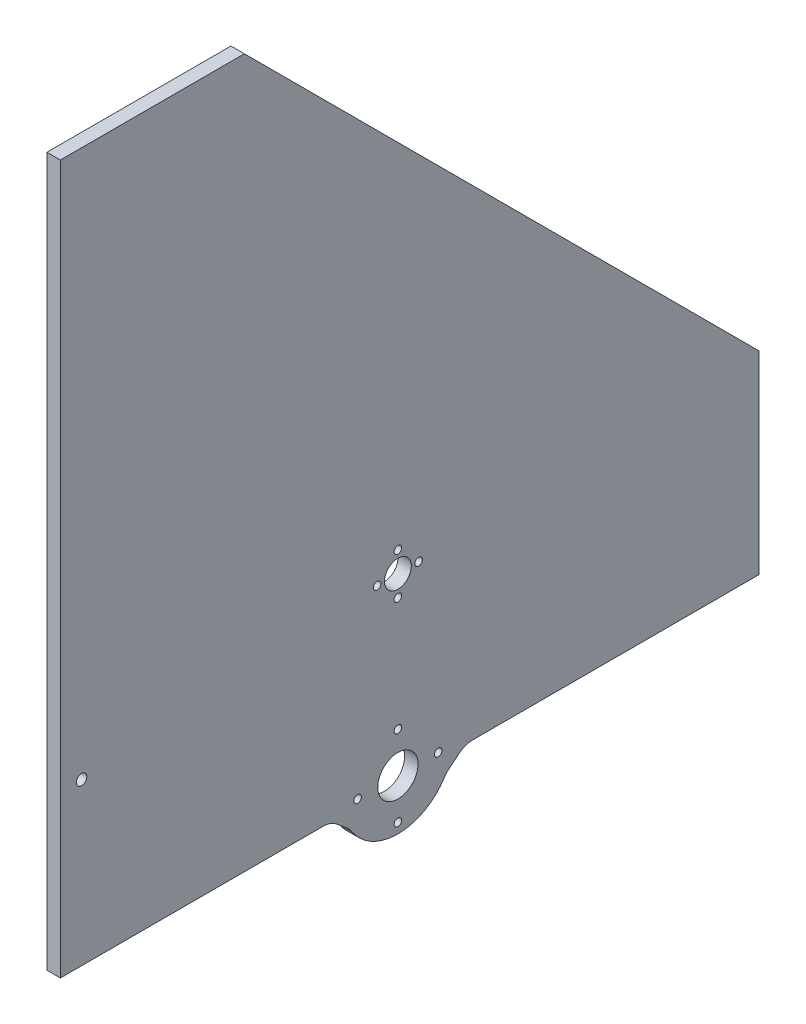
SolidWorks part; units mm, degrees
ref_plane "Front Plane" through (0, 0, 0) normal (0, 0, 1) x (1, 0, 0)
ref_plane "Top Plane" through (0, 0, 0) normal (0, 1, 0) x (1, 0, 0)
ref_plane "Right Plane" through (0, 0, 0) normal (1, 0, 0) x (0, 0, -1)
sketch "Sketch1" plane through (0, 0, 0) normal (1, 0, 0) x (0, 0, -1)
  line L0 (330.2, 112.3614) -> (86.9614, 355.6)
  line L1 (0, 0) -> (330.2, 0)
  line L2 (0, 0) -> (0, 355.6)
  line L3 (0, 355.6) -> (86.9614, 355.6)
  line L4 (330.2, 0) -> (330.2, 112.3614)
  point P1 (171.4728, 228.6)
  point P7 (105.7678, 228.6)
  point P8 (182.6629, 228.6)
  point P9 (110.0595, 228.6)
  point P10 (330.2, 66.1679)
  point P11 (148.4572, 228.6)
  point P12 (161.5636, 228.6)
  point P13 (172.5781, 228.6)
  point P14 (113.9067, 323.85)
  point P15 (113.028, 323.85)
  point P16 (86.9614, 355.6)
  dimension "D3" = 135
  dimension "D1" = 330.2
  dimension "D2" = 355.6
extrude "Main Plate Size" add sketch "Sketch1" along normal blind 6.35
sketch "Sketch2" plane through (6.35, 0, 0) normal (1, 0, 0) x (0, 0, -1)
  line L0 (178.562, 23.8252) -> (159.512, 42.8752) construction
  line L1 (0, 0) -> (330.2, 0) construction
  line L2 (178.562, 23.8252) -> (159.512, 4.7752) construction
  line L3 (159.512, 42.8752) -> (140.462, 23.8252) construction
  line L4 (159.512, 4.7752) -> (140.462, 23.8252) construction
  line L5 (178.562, 23.8252) -> (140.462, 23.8252) construction
  line L6 (159.512, 42.8752) -> (159.512, 4.7752) construction
  line L7 (0, 355.6) -> (0, 0) construction
  line L9 (0, 20.8026) -> (134.112, 20.8026)
  line L10 (184.912, 20.8026) -> (330.2, 20.8026)
  line L11 (330.2, 0) -> (330.2, 112.3614) construction
  line L12 (0, 20.8026) -> (0, 0)
  line L13 (330.2, 0) -> (330.2, 20.8026)
  line L15 (0, 0) -> (177.8, 0)
  line L16 (177.8, 0) -> (330.2, 0)
  circle A0 centre (159.512, 23.8252) radius 9.525
  circle A1 centre (159.512, 42.8752) radius 1.778
  circle A2 centre (178.562, 23.8252) radius 1.778
  circle A3 centre (159.512, 4.7752) radius 1.778
  circle A4 centre (140.462, 23.8252) radius 1.778
  arc A5 (134.112, 20.8026) -> (184.912, 20.8026) centre (159.512, 25.908) ccw
  point P24 (134.112, 20.8026)
  line M11 (0, 355.6) -> (0, 0)
  line M12 (0, 0) -> (330.2, 0)
  line M13 (330.2, 0) -> (330.2, 112.3614)
  dimension "D1" = 19.05
  dimension "D2" = 3.556
  dimension "D6" = 25.908
  dimension "D3" = 38.1
  dimension "D4" = 159.512
  dimension "D5" = 5.1054
  dimension "D7" = 2.0828
extrude "Bottom Shaft Mounting Holes" cut sketch "Sketch2" against normal through all contours A5 L9 M11 M12 | A5 L10 M12 M13 | A0 | A3 | A2 | A1 | A4 region at (6.35, 10.1874, -254.2605) region at (6.35, 10.1704, -70.3601) region at (6.35, 23.8252, -159.512) region at (6.35, 42.8752, -159.512) region at (6.35, 23.8252, -178.562) region at (6.35, 4.7752, -159.512) region at (6.35, 23.8252, -140.462)
sketch "Sketch3" plane through (6.35, 0, 0) normal (1, 0, 0) x (0, 0, -1)
  line L0 (159.512, 23.8252) -> (159.512, 106.5022) construction
  line L2 (159.512, 116.2812) -> (149.733, 106.5022) construction
  line L3 (149.733, 106.5022) -> (159.512, 96.7232) construction
  line L4 (159.512, 96.7232) -> (169.291, 106.5022) construction
  line L5 (169.291, 106.5022) -> (159.512, 116.2812) construction
  circle A0 centre (159.512, 106.5022) radius 6.35
  circle A1 centre (159.512, 106.5022) radius 9.779 construction
  circle A2 centre (149.733, 106.5022) radius 1.778
  circle A3 centre (159.512, 116.2812) radius 1.778
  circle A4 centre (169.291, 106.5022) radius 1.778
  circle A5 centre (159.512, 96.7232) radius 1.778
  dimension "D2" = 12.7
  dimension "D3" = 19.558
  dimension "D4" = 3.556
  dimension "D1" = 82.677
extrude "Top Battery Box Mounting Holes" cut sketch "Sketch3" against normal through all
chamfer "This is to match the idiotic Design of B Box" distance 6.35 distance2 6.35 2 edges at (3.175, 20.8026, -184.912) (3.175, 20.8026, -134.112)
fillet "This is to match the idiotic Design of B Box2" radius 10 4 edges at (3.175, 20.8026, -191.262) (3.175, 13.366, -182.1818) (3.175, 13.366, -136.8422) (3.175, 20.8026, -127.762)
sketch "Sketch4" plane through (6.35, 0, 0) normal (1, 0, 0) x (0, 0, -1)
  line L0 (0, 355.6) -> (0, 20.8026) construction
  line L1 (20, 87.0026) -> (0, 87.0026) construction
  line L2 (20, 87.0026) -> (20, 107.0026) construction
  line L3 (20, 107.0026) -> (0, 107.0026) construction
  line L4 (0, 87.0026) -> (0, 107.0026) construction
  line L5 (20, 87.0026) -> (0, 107.0026) construction
  line L6 (20, 107.0026) -> (0, 87.0026) construction
  line L7 (0, 20.8026) -> (124.1896, 20.8026) construction
  circle A0 centre (10, 97.0026) radius 2.5
  point P0 (10, 97.0026)
  dimension "D2" = 5
  dimension "D1" = 20
  dimension "D3" = 76.2
extrude "20mm Extrusion Mount" cut sketch "Sketch4" against normal through all
sketch "Sketch5" plane through (6.35, 0, 0) normal (1, 0, 0) x (0, 0, -1)
  line L0 (20, 87.0026) -> (0, 87.0026) construction
  line L1 (20, 87.0026) -> (0, 87.0026)
  line L2 (20, 87.0026) -> (20, 20.8026)
  line L3 (0, 20.8026) -> (124.1896, 20.8026) construction
  line L4 (0, 87.0026) -> (0, 20.8026)
  line L5 (0, 20.8026) -> (20, 20.8026)
